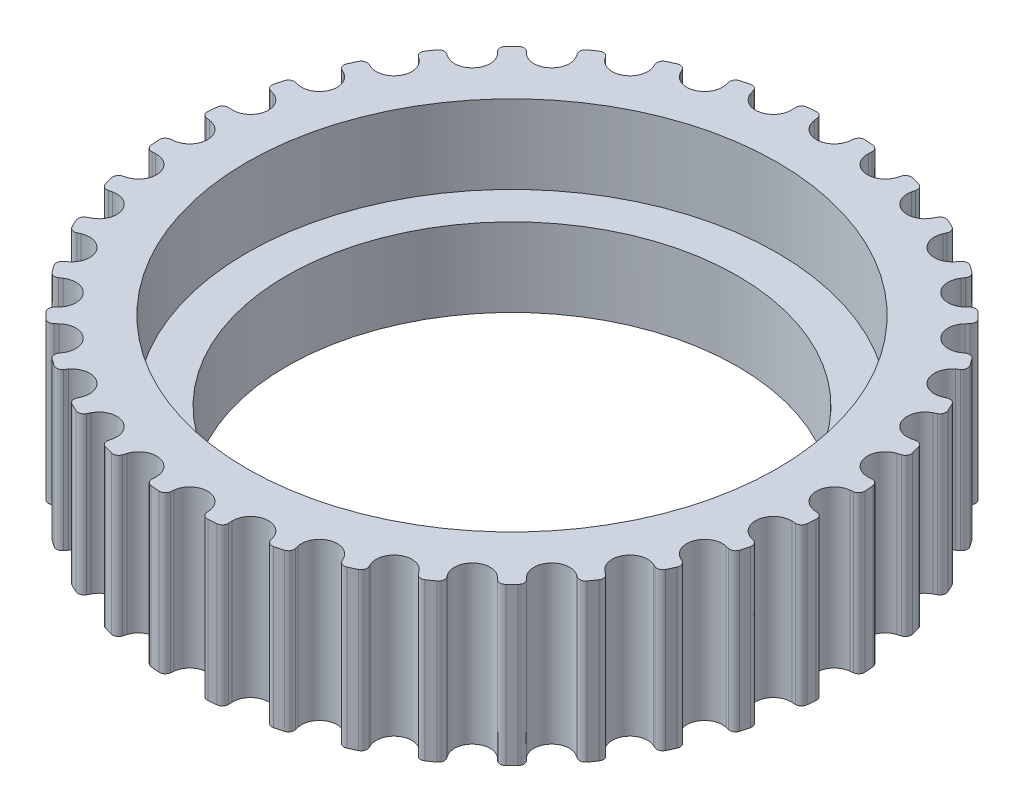
SolidWorks part; units mm, degrees
material "6061 合金"
ref_plane "前视基准面" through (0, 0, 0) normal (0, 0, 1) x (1, 0, 0)
ref_plane "上视基准面" through (0, 0, 0) normal (0, 1, 0) x (1, 0, 0)
ref_plane "右视基准面" through (0, 0, 0) normal (1, 0, 0) x (0, 0, -1)
ref_axis "基准轴1" through (0, -44, 0) along (0, 1, 0)
sketch "草图1" plane through (0, 0, 0) normal (0, 1, 0) x (1, 0, 0)
  circle A0 centre (0, 0) radius 16.8
extrude "凸台-拉伸1" add sketch "草图1" along normal mid plane 8
sketch "草图2" plane through (0, 0, 0) normal (0, 1, 0) x (1, 0, 0)
  line B0 (-0.9032, 16.3191) -> (-0.9244, 16.4912)
  line B1 (0.9032, 16.3191) -> (0.9244, 16.4912)
  arc B2 (-0.9032, 16.3191) -> (0.9032, 16.3191) centre (0, 16.43) ccw
  arc B3 (-1.2443, 16.7539) -> (1.2443, 16.7539) centre (0, 0) cw
  arc B4 (-0.9244, 16.4912) -> (-1.2443, 16.7539) centre (-1.2221, 16.4547) ccw
  arc B5 (1.2443, 16.7539) -> (0.9244, 16.4912) centre (1.2221, 16.4547) ccw
sketch_block_instance "HTD-1"
sketch_block "HTD" parameters "OD"=33.6, "D4"=0.3, "Rb"=0.91, "Rt"=0.3, "Dh"=1.28, "deg"=14
extrude "切除-拉伸1" cut sketch "草图2" against normal mid plane 100
pattern_circular "阵列(圆周)1" count 36 over 360 about axis through (0, -44, 0) along (0, 1, 0) of "切除-拉伸1"
sketch "草图4" plane through (0, 4, 0) normal (0, 1, 0) x (1, 0, 0)
  circle A0 centre (0, 0) radius 13.525
  dimension "D1" = 27.05
extrude "切除-拉伸2" cut sketch "草图4" against normal blind 4
sketch "草图6" plane through (0, -4, 0) normal (0, 1, 0) x (1, 0, 0)
  circle A0 centre (0, 0) radius 23
  dimension "D1" = 46
extrude "凸台-拉伸2" [suppressed] add sketch "草图6" against normal blind 5
sketch "草图7" [suppressed] plane through (0, -3.5, 0) normal (0, 1, 0) x (1, 0, 0)
  circle A0 centre (0, 0) radius 12.5 construction
  circle A1 centre (0, 0) radius 12.5
extrude "切除-拉伸3" [suppressed] cut sketch "草图7" against normal through all
sketch "草图9" [suppressed] plane through (0, -8.5, 0) normal (0, -1, 0) x (1, 0, 0)
  circle A0 centre (0, 0) radius 16
  dimension "D1" = 32
extrude "切除-拉伸5" [suppressed] cut sketch "草图9" against normal blind 3
sketch "草图10" [suppressed] plane through (0, -8.5, 0) normal (0, -1, 0) x (1, 0, 0)
  circle A0 centre (0, 20) radius 1.6
  circle A1 centre (17.3205, 10) radius 1.6
  circle A2 centre (17.3205, -10) radius 1.6
  circle A3 centre (0, -20) radius 1.6
  circle A4 centre (-17.3205, -10) radius 1.6
  circle A5 centre (-17.3205, 10) radius 1.6
  point P15 (0, 0)
  dimension "D1" = 20
  dimension "D2" = 6
extrude "切除-拉伸6" [suppressed] cut sketch "草图10" against normal through all
sketch "草图11" [suppressed] plane through (0, -3.5, 0) normal (0, 1, 0) x (1, 0, 0)
  line L0 (-2.9, 20) -> (-2.9, 25.6328)
  line L1 (-2.9, 25.6328) -> (2.9, 25.6328)
  line L2 (2.9, 25.6328) -> (2.9, 20)
  line L3 (15.8705, 12.5115) -> (20.7487, 15.3279)
  line L4 (20.7487, 15.3279) -> (23.6487, 10.3049)
  line L5 (23.6487, 10.3049) -> (18.7705, 7.4885)
  line L6 (18.7705, -7.4885) -> (23.6487, -10.3049)
  line L7 (23.6487, -10.3049) -> (20.7487, -15.3279)
  line L8 (20.7487, -15.3279) -> (15.8705, -12.5115)
  line L9 (2.9, -20) -> (2.9, -25.6328)
  line L10 (2.9, -25.6328) -> (-2.9, -25.6328)
  line L11 (-2.9, -25.6328) -> (-2.9, -20)
  line L12 (-15.8705, -12.5115) -> (-20.7487, -15.3279)
  line L13 (-20.7487, -15.3279) -> (-23.6487, -10.3049)
  line L14 (-23.6487, -10.3049) -> (-18.7705, -7.4885)
  line L15 (-18.7705, 7.4885) -> (-23.6487, 10.3049)
  line L16 (-23.6487, 10.3049) -> (-20.7487, 15.3279)
  line L17 (-20.7487, 15.3279) -> (-15.8705, 12.5115)
  arc A0 (-2.9, 20) -> (2.9, 20) centre (0, 20) ccw
  arc A6 (15.8705, 12.5115) -> (18.7705, 7.4885) centre (17.3205, 10) ccw
  arc A7 (18.7705, -7.4885) -> (15.8705, -12.5115) centre (17.3205, -10) ccw
  arc A8 (2.9, -20) -> (-2.9, -20) centre (0, -20) ccw
  arc A9 (-15.8705, -12.5115) -> (-18.7705, -7.4885) centre (-17.3205, -10) ccw
  arc A10 (-18.7705, 7.4885) -> (-15.8705, 12.5115) centre (-17.3205, 10) ccw
  point P33 (0, 0)
  dimension "D1" = 5.8
  dimension "D2" = 6
extrude "切除-拉伸9" [suppressed] cut sketch "草图11" against normal blind 3
sketch "草图13" plane through (0, -4, 0) normal (0, -1, 0) x (1, 0, 0)
  circle A0 centre (0, 0) radius 11.5
  dimension "D1" = 23
extrude "切除-拉伸10" cut sketch "草图13" against normal blind 19.5
sketch "草图14" plane through (0, -4, 0) normal (0, -1, 0) x (1, 0, 0)
  line L0 (7.1, 15.226) -> (3.2108, 6.8856) construction
  circle A0 centre (0, 0) radius 14 construction
  circle A1 centre (5.9167, 12.6883) radius 1.25
  circle A3 centre (13.9467, 1.2202) radius 1.25
  circle A4 centre (8.0301, -11.4681) radius 1.25
  circle A5 centre (-5.9167, -12.6883) radius 1.25
  circle A6 centre (-13.9467, -1.2202) radius 1.25
  circle A7 centre (-8.0301, 11.4681) radius 1.25
  arc A8 (7.2993, 15.1314) -> (6.8995, 15.3179) centre (0, 0) ccw construction
  point P17 (0, 0)
  dimension "D1" = 28
  dimension "D2" = 2.5
  dimension "D3" = 6
extrude "切除-拉伸11" cut sketch "草图14" against normal blind 3
sketch "草图15" plane through (0, 0, 0) normal (0, 1, 0) x (1, 0, 0)
  circle A0 centre (0, 0) radius 14
extrude "切除-拉伸12" cut sketch "草图15" against normal blind 1
sketch "草图16" plane through (0, -1, 0) normal (0, 1, 0) x (1, 0, 0)
  circle A0 centre (0, 0) radius 11.5
  circle A1 centre (0, 0) radius 14
extrude "凸台-拉伸3" add sketch "草图16" along normal blind 1
